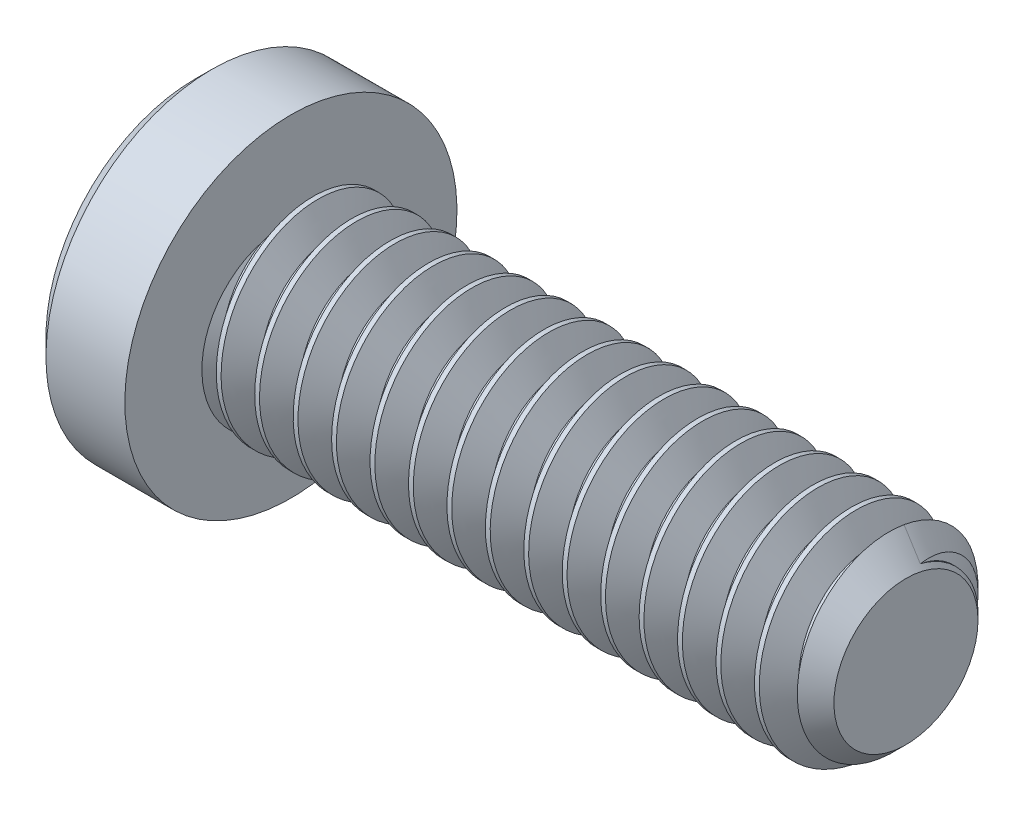
SolidWorks part; units mm, degrees
material "AISI 4340 Steel, normalized"
ref_plane "Front Plane" through (0, 0, 0) normal (0, 0, 1) x (1, 0, 0)
ref_plane "Top Plane" through (0, 0, 0) normal (0, 1, 0) x (1, 0, 0)
ref_plane "Right Plane" through (0, 0, 0) normal (1, 0, 0) x (0, 0, -1)
sketch "Sketch1" plane through (0, 0, 0) normal (0, 0, 1) x (1, 0, 0)
  line L0 (6.35, 0) -> (-6.35, 0) construction
  line L1 (6.35, 2.0828) -> (6.35, -2.0828) construction
  line L2 (-6.35, 3.429) -> (-6.35, -3.429) construction
  line L3 (-6.35, 3.429) -> (-7.9788, 3.429) construction
  line L4 (-7.9788, 3.429) -> (-8.3344, 3.0734) construction
  line L5 (-8.3344, 3.0734) -> (-8.3344, -3.0734) construction
  line L6 (-8.3344, -3.0734) -> (-7.9788, -3.429) construction
  line L7 (-7.9788, -3.429) -> (-6.35, -3.429) construction
  point P7 (-6.8104, 0)
  point P12 (3.175, -2.0828)
  dimension "D1" = 45
  dimension "D2" = 3.175
  dimension "Dec." = 4.1656
  dimension "Length" = 12.7
  dimension "Head Dia" = 6.858
  dimension "Head Height" = 1.9844
  dimension "Hex Depth" = 1.524
  dimension "Chamfer" = 0.3556
ref_plane "Plane1" through (6.35, 0, 0) normal (1, 0, 0) x (0, 0, -1)
ref_plane "Plane2" through (-8.3344, 0, 0) normal (1, 0, 0) x (0, 0, -1)
sketch "Sketch2" plane through (6.35, 0, 0) normal (1, 0, 0) x (0, 0, -1)
  circle A0 centre (0, 0) radius 2.0828
extrude "Boss-Extrude1" add sketch "Sketch2" against normal up to vertex (12.7 mm away) up to point (-6.35, 0, 0)
sketch "Sketch3" plane through (6.35, 0, 0) normal (1, 0, 0) x (0, 0, -1)
  circle A0 centre (0, 0) radius 2.0828 construction
  circle A1 centre (0, 0) radius 2.0828
curve "Helix/Spiral1" pitch 0.7937 height 13.4937 turns 17 parameters "Pitch"=0.7937
chamfer "Chamfer1" distance 0.5953 angle 45 1 edges at (6.35, 0, -2.0828)
sketch "Sketch5" plane through (0, 0, 0) normal (0, 0, 1) x (1, 0, 0)
  line L0 (6.0027, 2.0828) -> (6.6973, 2.0828)
  line L1 (6.6973, 2.0828) -> (6.3996, 1.5672)
  line L2 (6.3996, 1.5672) -> (6.3004, 1.5672)
  line L3 (6.3004, 1.5672) -> (6.0027, 2.0828)
  line L4 (6.35, 1.5672) -> (6.35, 2.0828) construction
  line L5 (6.1516, 1.825) -> (6.5484, 1.825) construction
  dimension "D1" = 60
  dimension "D2" = 0.3969
  dimension "D3" = 0.0992
sweep "Cut-Sweep1" cut profiles "Sketch5" path "Helix/Spiral1"
sketch "Sketch4" plane through (-8.3344, 0, 0) normal (1, 0, 0) x (0, 0, -1)
  line L0 (-3.429, 0.7937) -> (3.429, 0.7937) construction
  line L1 (0, 1.1457) -> (-0.9922, 0.5728)
  line L2 (-0.9922, 0.5728) -> (-0.9922, -0.5728)
  line L3 (-0.9922, -0.5728) -> (0, -1.1457)
  line L4 (0, -1.1457) -> (0.9922, -0.5728)
  line L5 (0.9922, -0.5728) -> (0.9922, 0.5728)
  line L6 (0.9922, 0.5728) -> (0, 1.1457)
  line L7 (0, 0) -> (0, 0.7937) construction
  circle A0 centre (0, 0) radius 0.9922 construction
  dimension "D1" = 6.858
  dimension "Hex Size" = 1.9844
  dimension "D2" = 0.7937
sketch "Sketch6" plane through (0, 0, 0) normal (0, 0, 1) x (1, 0, 0)
  line L0 (-7.9788, 3.429) -> (-8.3344, 3.0734) construction
  line L1 (-6.35, 3.429) -> (-7.9788, 3.429) construction
  line L2 (-6.35, 3.429) -> (-6.35, -3.429) construction
  line L3 (-8.3344, 3.0734) -> (-8.3344, -3.0734) construction
  line L4 (-7.9788, 3.429) -> (-8.3344, 3.0734)
  line L5 (-6.35, 3.429) -> (-7.9788, 3.429)
  line L6 (-6.35, 3.429) -> (-6.35, 0)
  line L7 (-8.3344, 3.0734) -> (-8.3344, 0)
  line L8 (-6.35, 0) -> (-8.3344, 0) construction
  line L9 (-6.35, 0) -> (-8.3344, 0)
revolve "Revolve1" add sketch "Sketch6" angle 360 about L8
extrude "Cut-Extrude1" cut sketch "Sketch4" along normal up to vertex (1.524 mm away) up to point (-6.8104, 0, 0)
sketch "Sketch8" plane through (-8.3344, 0, 0) normal (-1, 0, 0) x (0, 0, 1)
  circle A1 centre (0, 0) radius 1.1457
extrude "Cut-Extrude2" cut sketch "Sketch8" against normal through all draft 45
equation "\"D3@Helix/Spiral1\" = \"Length@Sketch1\"+\"Pitch@Helix/Spiral1\""
equation "\"D3@Sketch5\" = \"Pitch@Helix/Spiral1\"*.125"
equation "\"D2@Sketch5\" = \"Pitch@Helix/Spiral1\"*.50"
equation "\"D1@Chamfer1\" = \"Pitch@Helix/Spiral1\"*.75"
equation "\"D2@Sketch1\" = \"Pitch@Helix/Spiral1\"*4"
equation "\"D1@Sketch4\" = \"Head Dia@Sketch1\""
